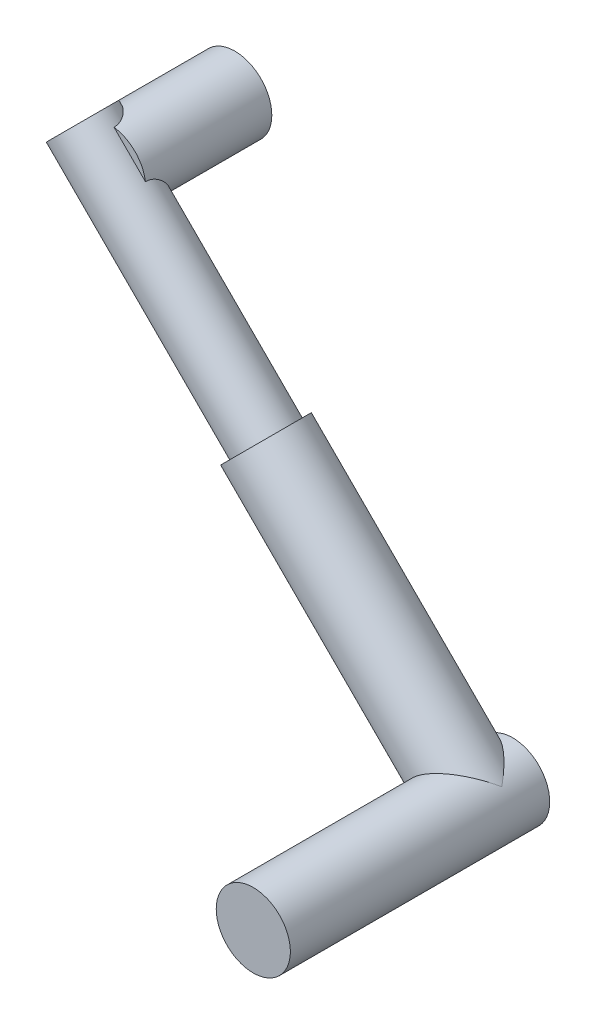
SolidWorks part; units mm, degrees
ref_plane "Front Plane" through (0, 0, 0) normal (0, 0, 1) x (1, 0, 0)
ref_plane "Top Plane" through (0, 0, 0) normal (0, 1, 0) x (1, 0, 0)
ref_plane "Right Plane" through (0, 0, 0) normal (1, 0, 0) x (0, 0, -1)
sketch "Sketch2" plane through (0, 0, 0) normal (0, 0, 1) x (1, 0, 0)
  circle A0 centre (0, 0) radius 25
extrude "Boss-Extrude1" add sketch "Sketch2" along normal blind 85
ref_plane "Plane2" through (-17.6777, 17.6777, 0) normal (-0.7071, 0.7071, 0) x (0, 0, -1)
sketch "Sketch6" plane through (-17.6777, 17.6777, 0) normal (-0.7071, 0.7071, 0) x (0, 0, -1)
  circle A0 centre (-84.9937, 0) radius 20
  dimension "D1" = 40
extrude "Boss-Extrude4" add sketch "Sketch6" against normal blind 175
sketch "Sketch7" plane through (106.066, -106.066, 0) normal (0.7071, -0.7071, 0) x (0, 0, -1)
  circle A0 centre (-84.9937, 0) radius 25
  dimension "D1" = 50
extrude "Boss-Extrude5" add sketch "Sketch7" along normal blind 200
ref_axis "Axis1" through (247.4874, -247.4874, 84.9937) along (-0.7071, 0.7071, 0)
ref_plane "Plane3" through (0, 0, 84.9937) normal (0, 0, -1) x (-0.7071, 0.7071, 0)
sketch "Sketch8" plane through (0, 0, 84.9937) normal (0, 0, -1) x (-0.7071, 0.7071, 0)
  line L0 (-350, 25) -> (-350, -25) construction
  circle A0 centre (-350, 0) radius 25
  dimension "D1" = 50
extrude "Boss-Extrude6" add sketch "Sketch8" along normal blind 25 and the other way blind 150
